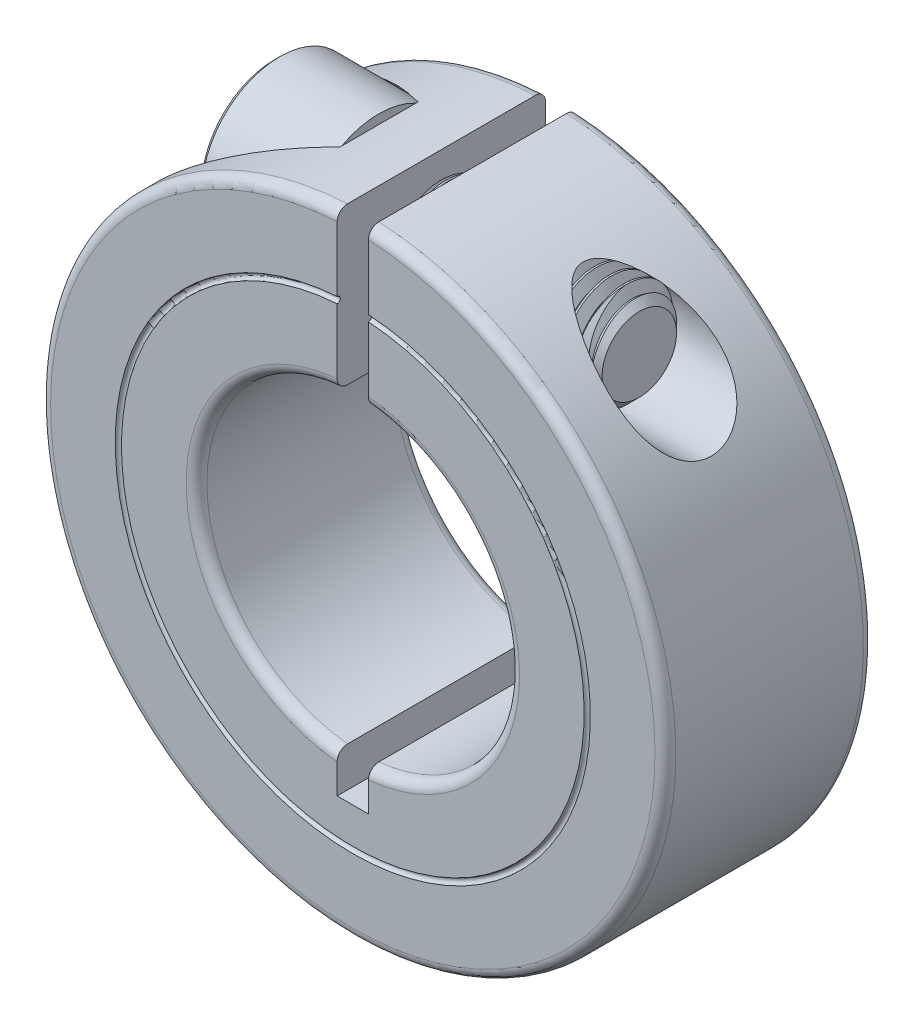
SolidWorks part; units mm, degrees
ref_plane "Front Plane" through (0, 0, 0) normal (0, 0, 1) x (1, 0, 0)
ref_plane "Top Plane" through (0, 0, 0) normal (0, 1, 0) x (1, 0, 0)
ref_plane "Right Plane" through (0, 0, 0) normal (1, 0, 0) x (0, 0, -1)
sketch "Sketch1" plane through (0, 0, 0) normal (0, 0, 1) x (1, 0, 0)
  line L0 (-0.9525, 9.4773) -> (-0.9525, 19.0262)
  line L2 (0.9525, 9.4773) -> (0.9525, 19.0262)
  line L3 (0, 0) -> (0, 9.4773) construction
  line L4 (0.9525, 9.4773) -> (-0.9525, 9.4773) construction
  line L5 (0, -19.05) -> (0, -9.525) construction
  line L6 (0, -9.525) -> (0, -14.2875) construction
  line L7 (-0.9525, -9.4773) -> (-0.9525, -11.9062)
  line L8 (-0.9525, -11.9062) -> (0.9525, -11.9062)
  line L9 (0.9525, -9.4773) -> (0.9525, -11.9062)
  line L10 (-0.9525, 14.2517) -> (0.9525, 14.2517) construction
  circle A0 centre (0, 0) radius 19.05 construction
  circle A1 centre (0, 0) radius 9.525 construction
  arc A3 (-0.9525, 19.0262) -> (0.9525, 19.0262) centre (0, 0) ccw
  arc A4 (0.9525, -9.4773) -> (0.9525, 9.4773) centre (0, 0) ccw
  arc A5 (-0.9525, 9.4773) -> (-0.9525, -9.4773) centre (0, 0) ccw
  point P4 (19.05, 0)
  point P5 (-19.05, 0)
  point P19 (0, -11.9062)
  dimension "Bore Dia" = 19.05
  dimension "OD" = 38.1
  dimension "Separation" = 1.905
extrude "Extrude1" add sketch "Sketch1" along normal mid plane 12.7
fillet "Fillet1" radius 0.635 6 edges at (0, -19.05, -6.35) (0, -19.05, 6.35) (-9.525, 0, -6.35) (-9.525, 0, 6.35) (9.525, 0, -6.35) (9.525, 0, 6.35)
sketch "Sketch2" plane through (0, 0, 0) normal (0, 1, 0) x (1, 0, 0)
  line L0 (0, 0) -> (-9.525, 0) construction
  line L1 (-9.525, 0) -> (-19.05, 0) construction
  line L2 (-14.2875, 6.35) -> (-14.2875, -6.35) construction
  line L3 (18.415, 6.35) -> (-18.415, 6.35) construction
  line L4 (-18.415, -6.35) -> (18.415, -6.35) construction
  line L5 (-19.05, 5.715) -> (-19.05, -5.715) construction
  line L6 (-9.525, 5.715) -> (-9.525, -5.715) construction
  line L8 (-14.478, -6.35) -> (-14.097, -6.35)
  line L9 (0, 6.35) -> (0, -6.35) construction
  line L10 (-0.9525, 6.35) -> (-10.16, 6.35) construction
  arc A1 (-14.097, -6.35) -> (-14.478, -6.35) centre (-14.2875, -6.35) ccw
  point P1 (-14.2875, 0)
  dimension "D2" = 0.1905
revolve "Cut-Revolve1" cut sketch "Sketch2" angle 360 about L9
sketch "Sketch3" plane through (0, 0, 0) normal (0, 0, 1) x (1, 0, 0)
  line L0 (19.05, 14.2517) -> (-19.05, 14.2517)
  line L1 (-19.05, 14.2517) -> (-19.05, 9.4257)
  line L2 (-19.05, 9.4257) -> (-4.7625, 9.4257)
  line L4 (-4.7625, 9.4257) -> (-4.7625, 11.0767)
  line L7 (-4.7625, 11.0767) -> (19.05, 11.0767)
  line L8 (19.05, 11.0767) -> (19.05, 14.2517)
  line L9 (-19.05, 14.2517) -> (-23.876, 14.2517) construction
  line L10 (-0.9525, 14.2517) -> (0.9525, 14.2517) construction
  dimension "D2" = 4.7625
  dimension "D4" = 9.652
  dimension "Screw Dia" = 6.35
revolve "Cut-Revolve2" cut sketch "Sketch3" angle 360 about L9
sketch "Sketch4" plane through (0, 0, 0) normal (0, 0, 1) x (1, 0, 0)
  line L0 (-11.1125, 14.2517) -> (-11.1125, 19.0142)
  line L2 (-11.1125, 19.0142) -> (-4.7625, 19.0142)
  line L3 (-4.7625, 19.0142) -> (-4.7625, 17.4267)
  line L4 (-4.7625, 17.4267) -> (11.1125, 17.4267)
  line L5 (-4.7625, 9.4257) -> (-4.7625, 11.0767) construction
  line L6 (11.1125, 17.4267) -> (11.1125, 14.2517)
  line L7 (-4.7625, 11.0767) -> (19.05, 11.0767) construction
  line L8 (11.1125, 14.2517) -> (-11.1125, 14.2517)
  line L9 (11.1125, 17.4267) -> (11.1125, 11.0767) construction
  line L10 (-11.1125, 14.2517) -> (-15.875, 14.2517) construction
  line L11 (-19.05, 14.2517) -> (-23.876, 14.2517) construction
  dimension "Head Ht" = 6.35
  dimension "Screw Lg" = 15.875
  dimension "Head Dia" = 9.525
revolve "Revolve1" add sketch "Sketch4" angle 360 about L8
sketch "Sketch5" plane through (-11.1125, 0, 0) normal (-1, 0, 0) x (0, -1, 0)
  line L1 (-12.8769, -2.3813) -> (-11.5021, 0)
  line L2 (-11.5021, 0) -> (-12.8769, 2.3812)
  line L3 (-12.8769, 2.3812) -> (-15.6265, 2.3812)
  line L4 (-15.6265, 2.3812) -> (-17.0013, 0)
  line L5 (-17.0013, 0) -> (-15.6265, -2.3813)
  line L6 (-15.6265, -2.3813) -> (-12.8769, -2.3813)
  circle A0 centre (-14.2517, 0) radius 2.3812 construction
  dimension "Hex" = 4.7625
extrude "Cut-Extrude1" cut sketch "Sketch5" against normal blind 4.7625
chamfer "Chamfer1" distance 0.3175 angle 45 1 edges at (-11.1125, 19.0142, 0)
sketch "Sketch6" plane through (11.1125, 0, 0) normal (1, 0, 0) x (0, 1, 0)
  circle A0 centre (14.2517, 0) radius 3.175 construction
  circle A1 centre (14.2517, 0) radius 3.175
  point P3 (17.4267, 0)
curve "Helix/Spiral1" pitch 0.9071 height 15.875 turns 17.5 parameters "Height"=15.875, "Pitch"=0.9071
sketch "Sketch7" plane through (0, 0, 0) normal (0, 0, 1) x (1, 0, 0)
  line L0 (11.5094, 16.7393) -> (11.0558, 17.5249) construction
  line L1 (11.0558, 17.5249) -> (11.9629, 17.5249) construction
  line L2 (11.9629, 17.5249) -> (11.5094, 16.7393) construction
  line L3 (11.1125, 17.4267) -> (11.9062, 17.4267) construction
  line L4 (11.4527, 16.8375) -> (11.5661, 16.8375)
  line L5 (11.5094, 17.5249) -> (11.5094, 17.4267) construction
  line L6 (11.5094, 16.8375) -> (11.5094, 16.7393) construction
  line L7 (11.4527, 16.8375) -> (11.0842, 17.4758)
  line L8 (11.0842, 17.4758) -> (11.9346, 17.4758)
  line L9 (11.9346, 17.4758) -> (11.5661, 16.8375)
  point P10 (11.5094, 17.4758)
  dimension "D1" = 0.9071
  dimension "D2" = 0.1134
chamfer "Chamfer2" distance 0.9071 angle 45 1 edges at (11.1125, 17.4267, 0)
sweep "Cut-Sweep1" cut profiles "Sketch7" path "Helix/Spiral1"
equation "\"D1@Sketch3\" = \"Screw Dia@Sketch3\""
equation "\"D1@Cut-Extrude1\" = \"Hex@Sketch5\""
equation "\"D1@Fillet1\" = \"Width@Extrude1\"*.05"
equation "\"D4@Sketch3\" = \"Head Dia@Sketch4\" + .005"
equation "\"Height@Helix/Spiral1\" = \"Screw Lg@Sketch4\""
equation "\"D1@Sketch7\" = \"Pitch@Helix/Spiral1\""
equation "\"D2@Sketch7\" = \"D1@Sketch7\"/8"
equation "\"D1@Chamfer2\" = \"Pitch@Helix/Spiral1\""
equation "\"Separation@Sketch1\" = \"Bore Dia@Sketch1\"/10"
equation "\"D2@Sketch3\" = \"Screw Dia@Sketch3\"*.750"
